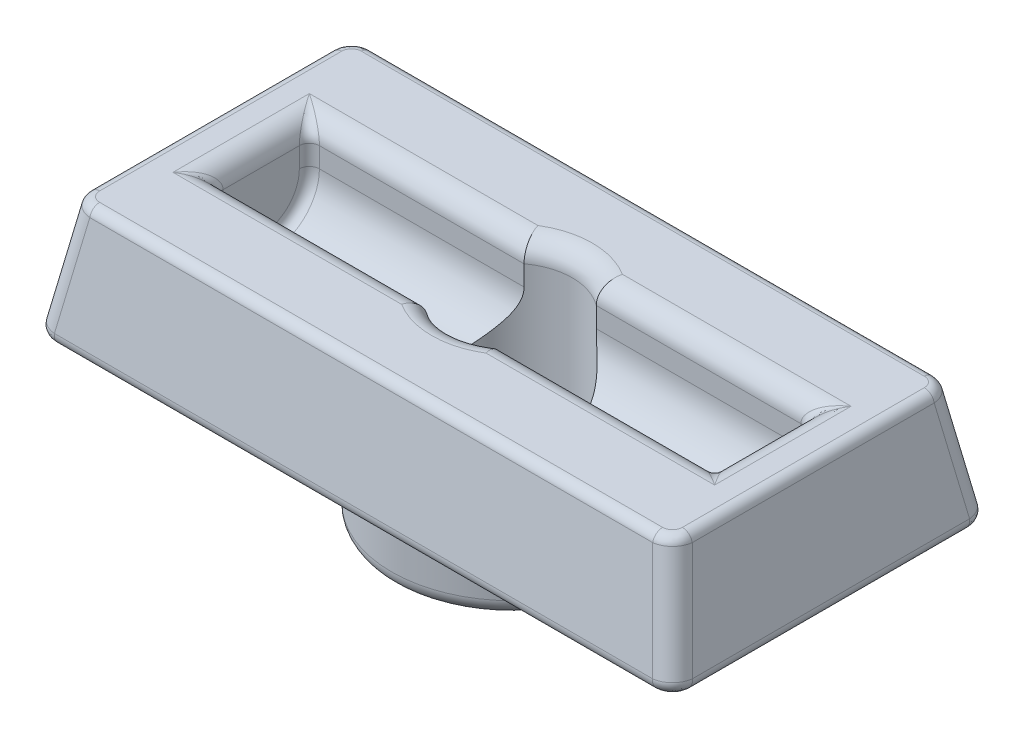
SolidWorks part; units mm, degrees
ref_plane "Front plane" through (0, 0, 0) normal (0, 0, 1) x (1, 0, 0)
ref_plane "Top plane" through (0, 0, 0) normal (0, 1, 0) x (1, 0, 0)
ref_plane "Right plane" through (0, 0, 0) normal (1, 0, 0) x (0, 0, -1)
ref_axis "Axis X" through (0, 0, 0) along (1, 0, 0)
ref_axis "Axis Y" through (0, 0, 0) along (0, 1, 0)
ref_axis "Axis Z" through (0, 0, 0) along (0, 0, 1)
sketch "Sketch1" plane through (0, 0, 0) normal (0, 1, 0) x (1, 0, 0)
  line L1 (-8, 4) -> (8, 4)
  line L2 (-8, 4) -> (-8, -4)
  line L3 (-8, -4) -> (8, -4)
  line L4 (8, 4) -> (8, -4)
  line L5 (-8, 4) -> (8, -4) construction
  line L6 (-8, -4) -> (8, 4) construction
  point P0 (0, 0)
  dimension "D1" = 8
  dimension "D2" = 16
extrude "Extrude1" add sketch "Sketch1" along normal blind 3 draft 10
sketch "Sketch2" plane through (0, 0, 0) normal (1, 0, 0) x (0, 0, -1)
  line L0 (-4, 0) -> (4, 0) construction
  line L1 (-3.471, 3) -> (3.471, 3) construction
  line L2 (-1.2, 2) -> (1.2, 2) construction
  line L3 (-1.2, 2) -> (-1.2, 3)
  line L4 (-1.2, 3) -> (1.2, 3)
  line L5 (1.2, 2) -> (1.2, 3)
  line L6 (0, 2) -> (0, 0) construction
  arc A0 (-1.2, 2) -> (1.2, 2) centre (0, 2) ccw
  arc A1 (0.6633, 3) -> (-1.2, 2) centre (0, 2) ccw construction
  arc A2 (1.2, 2) -> (0.6633, 3) centre (0, 2) ccw construction
  dimension "D2" = 2.4
  dimension "D1" = 2
extrude "Extrude2" cut sketch "Sketch2" against normal blind 6.25 and the other way blind 6.25
sketch "Sketch4" plane through (0, 0, 0) normal (0, -1, 0) x (1, 0, 0)
  circle A0 centre (0, 0) radius 3
  dimension "D1" = 6
extrude "Extrude4" add sketch "Sketch4" along normal blind 2
sketch "Sketch3" plane through (0, 3, 0) normal (0, 1, 0) x (1, 0, 0)
  circle A0 centre (0, 0) radius 1.5
  dimension "D1" = 3
extrude "Extrude3" cut sketch "Sketch3" against normal through all
fillet "Fillet1" radius 0.5 12 edges at (-3.575, 3, -1.2) (-6.25, 3, 0) (-3.575, 3, 1.2) (0, 3, 1.5) (3.575, 3, 1.2) (6.25, 3, 0) (3.575, 3, -1.2) (0, 3, -1.5) (-7.7355, 1.5, -3.7355) (-7.7355, 1.5, 3.7355) (7.7355, 1.5, 3.7355) (7.7355, 1.5, -3.7355)
fillet "Fillet3" radius 0.25 26 edges at (-7.3277, 3, -3.3277) (0, 3, -3.471) (7.3277, 3, -3.3277) (7.471, 3, 0) (7.3277, 3, 3.3277) (0, 3, 3.471) (-7.3277, 3, 3.3277) (6.3964, 2.8536, 1.3464) (6.25, 2.25, 1.2) (6.3964, 2.8536, -1.3464) (6.25, 2.25, -1.2) (-6.3964, 2.8536, 1.3464) (-6.25, 2.25, 1.2) (-6.3964, 2.8536, -1.3464) (-6.25, 2.25, -1.2) (-7.471, 3, 0) (6.25, 0.8, 0) (-6.25, 0.8, 0) (0, 0, 4) (7.8567, 0, 3.8567) (8, 0, 0) (7.8567, 0, -3.8567) (-7.8567, 0, 3.8567) (-8, 0, 0) (-7.8567, 0, -3.8567) (0, 0, -4)
fillet "Fillet4" radius 0.4 1 edges at (0, -2, -3)
equation "\"motor_D\"= 30'Motor diameter"
equation "\"motor_H\"= 13'Motor heigh"
equation "\"motor_d1\"= 25.4558'Seating diameter of screws on the fixed part of the motor"
equation "\"motor_s1\"= 2'Screws diameter on the fixed part of motor"
equation "\"motor_d2\"= 0'Seating diameter of screws on the moving part of the motor (if this parameter is not determine, write 0)"
equation "\"motor_s2\"= 2'Screws diameter on the moving part of motor"
equation "\"motor_Dc\"= 5'Central hole diameter of motor"
equation "\"bearing_d1\"= 6'Bearing inner diameter"
equation "\"bearing_d2\"= 17'Bearing external diameter"
equation "\"bearing h\"= 6'Bearing heigh"
equation "\"pin_d\"= 2'Pin diameter"
equation "\"pin_h\"= 12'Pin heigh"
equation "\"magnet_d1\"= 5'Magnet inner diameter"
equation "\"magnet_d2\"= 9.5'Magnet external diameter"
equation "\"magnet_h\"= 3'Magnet heigh"
equation "\"D1@Sketch1\"=\"pin_d\"+6"
equation "\"D2@Sketch1\"=\"pin_h\"+4"
equation "\"D1@Extrude1\"=\"pin_d\"+1"
equation "\"D1@Sketch2\"=\"pin_d\"/2+1"
equation "\"D2@Sketch2\"=\"pin_d\"+\"print_offset\"*2"
equation "\"D1@Extrude2\"=(\"pin_h\"+0.5)/2"
equation "\"D2@Extrude2\"=(\"pin_h\"+0.5)/2"
equation "\"D1@Sketch3\"= \"bearing_d1\" / 2"
equation "\"D1@Sketch4\"=\"bearing_d1\""
equation "\"D1@Extrude4\"=\"bearing h\"/3"
equation "\"motor_a2\"= 10'Seating parameter in rectangle of screws on the moving part of the motor"
equation "\"motor_b2\"= 22'Seating parameter in rectangle of screws on the moving part of the motor"
equation "\"motor_cmd\"= 12'Central magnet mount diameter"
equation "\"motor_cmh\"= 1.4'Central magnet mount heigh (if not write 0)"
equation "\"motor_whR\"= 10'Distance from center of motor to wires"
equation "\"print_offset\"= 0.2'Offset for printing holes"
equation "\"ft_sensor_d1\"= 9.8"
equation "\"ft_sensor_d2\"= 24.9"
equation "\"ft_sensor_d3\"= 22.6'Inner diameter of "
equation "\"ft_sensor_h\"= 7.1"
equation "\"ft_sensor_whD\" = 5"
